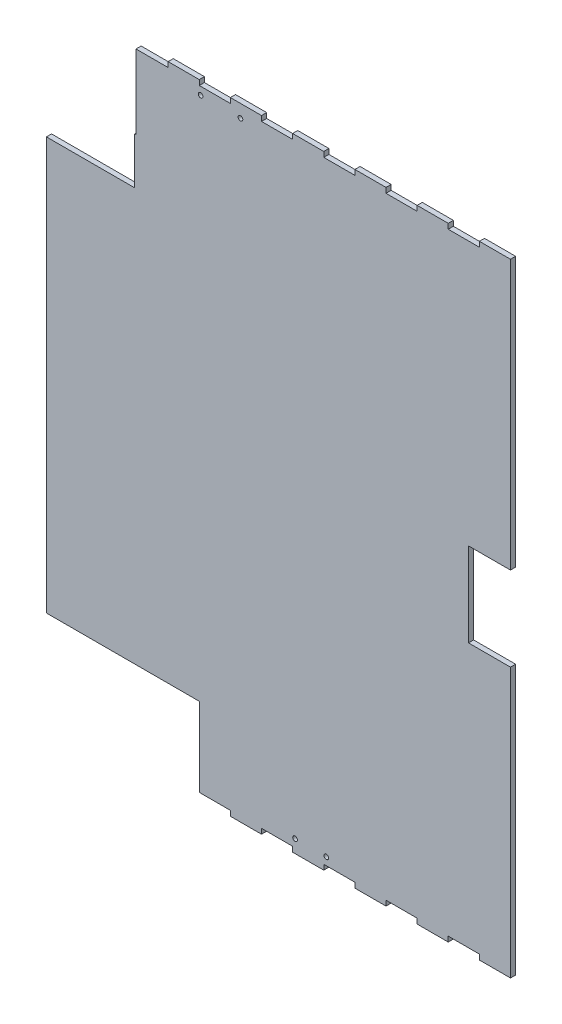
SolidWorks part; units mm, degrees
material "Balsa"
ref_plane "Front Plane" through (0, 0, 0) normal (0, 0, 1) x (1, 0, 0)
ref_plane "Top Plane" through (0, 0, 0) normal (0, 1, 0) x (1, 0, 0)
ref_plane "Right Plane" through (0, 0, 0) normal (1, 0, 0) x (0, 0, -1)
sketch "Sketch1" plane through (0, 0, 0) normal (0, 0, 1) x (1, 0, 0)
  line L0 (-5.7823, -13) -> (25.5, -13)
  line L2 (-5.7823, 1) -> (-5.7823, -13)
  line L5 (24.5, -14) -> (-24.5, -14) construction
  line L6 (323.7481, -265) -> (323.7481, 30)
  line L7 (-5.8246, -265) -> (65.6329, -265)
  line L8 (-5.8246, -265) -> (-5.8246, -225)
  line L11 (-5.8246, -265) -> (65.6329, -225) construction
  line L12 (-5.8246, -225) -> (65.6329, -265) construction
  line L15 (323.7481, -265) -> (25.5, -265)
  line L16 (25.5, 1) -> (25.5, -265)
  line L17 (-5.8246, -225) -> (25.5, -225)
  line L18 (-24.5, -224) -> (24.5, -224) construction
  line L19 (-5.7823, 1) -> (25.5, 1)
  line L20 (24.5, -224) -> (24.5, -14) construction
  line L21 (-85.1981, 31) -> (50.7481, 31) construction
  line L23 (25.5, 1) -> (25.5, 30)
  line L24 (25.5, 30) -> (323.7481, 30)
  line L27 (277.3251, 57) -> (277.3251, -295) construction
  line L28 (26.2777, -266) -> (-26.2882, -266) construction
  line L30 (-63.4467, 81) -> (255.5737, 81) construction
  line L31 (83.0863, 30) -> (323.7481, 30)
  line L32 (83.0863, 30) -> (83.0863, 77.7)
  line L33 (83.0863, 77.7) -> (323.7481, 77.7)
  line L34 (323.7481, 30) -> (323.7481, 77.7)
  line L35 (83.0863, 30) -> (323.7481, 77.7) construction
  line L36 (83.0863, 77.7) -> (323.7481, 30) construction
  line L37 (255.5737, -319) -> (-63.4467, -319) construction
  line L38 (323.7481, -265) -> (123.7481, -265)
  line L39 (323.7481, -265) -> (323.7481, -315.7)
  line L40 (323.7481, -315.7) -> (123.7481, -315.7)
  line L41 (123.7481, -265) -> (123.7481, -315.7)
  line L42 (323.7481, -265) -> (123.7481, -315.7) construction
  line L43 (323.7481, -315.7) -> (123.7481, -265) construction
  line L44 (50.7481, 31) -> (50.7481, -269) construction
  line L45 (83.0863, 31) -> (83.0863, -269) construction
  point P4 (32.4695, -6)
  point P10 (29.9042, -245)
  point P15 (48.1318, -132)
  point P24 (48.1318, 15.5)
  point P36 (203.4172, 53.85)
  point P42 (223.7481, -290.35)
  dimension "D1" = 1
  dimension "D2" = 1
  dimension "D3" = 1
  dimension "D4" = 1
  dimension "D5" = 1
  dimension "D6" = 31.3246
  dimension "D7" = 273
  dimension "D8" = 3.3
  dimension "D9" = 200
  dimension "D10" = 3.3
extrude "Boss-Extrude1" add sketch "Sketch1" along normal blind 3.3 contours L24 L23 L16 L7 L15 L6 | L15 L41 L40 L39 | L24 L34 L33 L32 region at (174.6241, -117.5, 0) region at (203.4172, 53.85, 0) region at (223.7481, -290.35, 0)
sketch "Sketch2" plane through (0, 0, 0) normal (0, 0, -1) x (-1, 0, 0)
  circle A0 centre (-150.2163, 72.7) radius 1.5
  circle A1 centre (-124.6149, 72.7) radius 1.5
  circle A2 centre (-205.3942, -310.7) radius 1.5
  circle A3 centre (-185.3098, -310.7) radius 1.5
  circle A4 centre (-150.2163, 72.7) radius 2 construction
  circle A5 centre (-124.6149, 72.7) radius 2 construction
  circle A6 centre (-205.3942, -310.7) radius 2 construction
  circle A7 centre (-185.3098, -310.7) radius 2 construction
  dimension "D1" = 3
  dimension "D2" = 3
  dimension "D3" = 3
  dimension "D4" = 3
extrude "Cut-Extrude1" cut sketch "Sketch2" against normal through all
sketch "Sketch3" plane through (119.3915, 0, 256.0358) normal (0.4226, 0, 0.9063) x (0.9063, 0, -0.4226)
  line L1 (293.4595, -146) -> (268.9595, -146)
  line L2 (293.4595, -146) -> (293.4595, -92)
  line L3 (293.4595, -92) -> (268.9595, -92)
  line L4 (268.9595, -146) -> (268.9595, -92)
  line L5 (293.4595, -146) -> (268.9595, -92) construction
  line L6 (293.4595, -92) -> (268.9595, -146) construction
  point P4 (281.2095, -119)
extrude "Cut-Extrude2" cut sketch "Sketch3" against normal through all both and the other way through all
sketch "Sketch4" plane through (0, 0, 0) normal (0, 0, -1) x (-1, 0, 0)
  line L1 (-323.7481, -92) -> (-296.7639, -92)
  line L2 (-323.7481, -92) -> (-323.7481, -146)
  line L3 (-323.7481, -146) -> (-296.7639, -146)
  line L4 (-296.7639, -92) -> (-296.7639, -146)
  line L5 (-323.7481, -92) -> (-296.7639, -146) construction
  line L6 (-323.7481, -146) -> (-296.7639, -92) construction
  point P4 (-310.256, -119)
extrude "Cut-Extrude3" cut sketch "Sketch4" against normal blind 10
sketch "Sketch6" plane through (0, 0, 3.3) normal (0, 0, 1) x (1, 0, 0)
  line L1 (25.5, 30) -> (82.2279, 30)
  line L2 (25.5, 30) -> (25.5, 0)
  line L3 (25.5, 0) -> (82.2279, 0)
  line L4 (82.2279, 30) -> (82.2279, 0)
  line L5 (25.5, 30) -> (82.2279, 0) construction
  line L6 (25.5, 0) -> (82.2279, 30) construction
  point P4 (53.864, 15)
extrude "Cut-Extrude4" cut sketch "Sketch6" against normal blind 10
sketch "Sketch7" plane through (0, 0, 0) normal (0, 0, -1) x (-1, 0, 0)
  line L0 (-203.7481, -315.7) -> (-183.7481, -315.7)
  line L1 (-163.7481, -315.7) -> (-143.7481, -315.7)
  line L2 (-163.7481, -315.7) -> (-163.7481, -319)
  line L3 (-163.7481, -319) -> (-143.7481, -319)
  line L4 (-143.7481, -315.7) -> (-143.7481, -319)
  line L5 (-163.7481, -315.7) -> (-143.7481, -319) construction
  line L6 (-163.7481, -319) -> (-143.7481, -315.7) construction
  line L7 (-103.7481, 77.7) -> (-123.7481, 77.7)
  line L8 (-103.7481, 77.7) -> (-103.7481, 81)
  line L9 (-103.7481, 81) -> (-123.7481, 81)
  line L10 (-123.7481, 77.7) -> (-123.7481, 81)
  line L11 (-103.7481, 77.7) -> (-123.7481, 81) construction
  line L12 (-103.7481, 81) -> (-123.7481, 77.7) construction
  line L13 (-203.7481, -315.7) -> (-203.7481, -319)
  line L14 (-203.7481, -319) -> (-183.7481, -319)
  line L15 (-183.7481, -315.7) -> (-183.7481, -319)
  line L16 (-143.7481, 77.7) -> (-163.7481, 77.7)
  line L17 (-143.7481, 77.7) -> (-143.7481, 81)
  line L18 (-143.7481, 81) -> (-163.7481, 81)
  line L19 (-163.7481, 77.7) -> (-163.7481, 81)
  line L20 (-203.7481, -315.7) -> (-183.7481, -319) construction
  line L21 (-203.7481, -319) -> (-183.7481, -315.7) construction
  line L22 (-143.7481, 77.7) -> (-163.7481, 81) construction
  line L23 (-143.7481, 81) -> (-163.7481, 77.7) construction
  line L24 (-243.7481, -315.7) -> (-223.7481, -315.7)
  line L25 (-243.7481, -315.7) -> (-243.7481, -319)
  line L26 (-243.7481, -319) -> (-223.7481, -319)
  line L27 (-223.7481, -315.7) -> (-223.7481, -319)
  line L28 (-183.7481, 77.7) -> (-203.7481, 77.7)
  line L29 (-183.7481, 77.7) -> (-183.7481, 81)
  line L30 (-183.7481, 81) -> (-203.7481, 81)
  line L31 (-203.7481, 77.7) -> (-203.7481, 81)
  line L32 (-243.7481, -315.7) -> (-223.7481, -319) construction
  line L33 (-243.7481, -319) -> (-223.7481, -315.7) construction
  line L34 (-183.7481, 77.7) -> (-203.7481, 81) construction
  line L35 (-183.7481, 81) -> (-203.7481, 77.7) construction
  line L36 (-283.7481, -315.7) -> (-263.7481, -315.7)
  line L37 (-283.7481, -315.7) -> (-283.7481, -319)
  line L38 (-283.7481, -319) -> (-263.7481, -319)
  line L39 (-263.7481, -315.7) -> (-263.7481, -319)
  line L40 (-223.7481, 77.7) -> (-243.7481, 77.7)
  line L41 (-223.7481, 77.7) -> (-223.7481, 81)
  line L42 (-223.7481, 81) -> (-243.7481, 81)
  line L43 (-243.7481, 77.7) -> (-243.7481, 81)
  line L44 (-283.7481, -315.7) -> (-263.7481, -319) construction
  line L45 (-283.7481, -319) -> (-263.7481, -315.7) construction
  line L46 (-223.7481, 77.7) -> (-243.7481, 81) construction
  line L47 (-223.7481, 81) -> (-243.7481, 77.7) construction
  line L48 (-323.7481, -315.7) -> (-303.7481, -315.7)
  line L49 (-323.7481, -315.7) -> (-323.7481, -319)
  line L50 (-323.7481, -319) -> (-303.7481, -319)
  line L51 (-303.7481, -315.7) -> (-303.7481, -319)
  line L52 (-263.7481, 77.7) -> (-283.7481, 77.7)
  line L53 (-263.7481, 77.7) -> (-263.7481, 81)
  line L54 (-263.7481, 81) -> (-283.7481, 81)
  line L55 (-283.7481, 77.7) -> (-283.7481, 81)
  line L56 (-323.7481, -315.7) -> (-303.7481, -319) construction
  line L57 (-323.7481, -319) -> (-303.7481, -315.7) construction
  line L58 (-263.7481, 77.7) -> (-283.7481, 81) construction
  line L59 (-263.7481, 81) -> (-283.7481, 77.7) construction
  line L60 (-143.7481, -315.7) -> (-143.7481, -319) construction
  line L61 (-303.7481, 77.7) -> (-323.7481, 77.7)
  line L62 (-303.7481, 77.7) -> (-303.7481, 81)
  line L63 (-303.7481, 81) -> (-323.7481, 81)
  line L64 (-323.7481, 77.7) -> (-323.7481, 81)
  line L65 (-303.7481, 77.7) -> (-323.7481, 81) construction
  line L66 (-303.7481, 81) -> (-323.7481, 77.7) construction
  point P4 (-193.7481, -317.35)
  point P11 (-113.7481, 79.35)
  point P19 (-233.7481, -317.35)
  point P24 (-153.7481, 79.35)
  point P29 (-273.7481, -317.35)
  point P34 (-193.7481, 79.35)
  point P39 (-313.7481, -317.35)
  point P44 (-233.7481, 79.35)
  point P49 (-353.7481, -317.35)
  point P54 (-273.7481, 79.35)
  point P62 (-313.7481, 79.35)
  dimension "D1" = 5
  dimension "D2" = 2
extrude "Boss-Extrude2" add sketch "Sketch7" against normal blind 3.3
